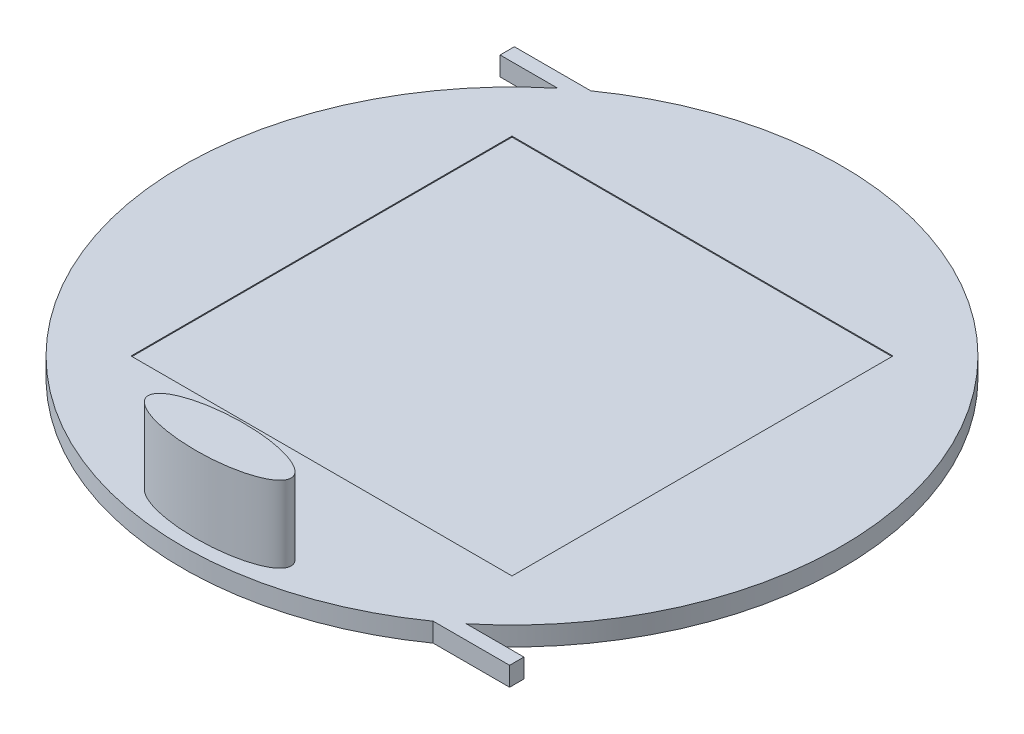
SolidWorks part; units mm, degrees
ref_plane "Front Plane" through (0, 0, 0) normal (0, 0, 1) x (1, 0, 0)
ref_plane "Top Plane" through (0, 0, 0) normal (0, 1, 0) x (1, 0, 0)
ref_plane "Right Plane" through (0, 0, 0) normal (1, 0, 0) x (0, 0, -1)
sketch "Sketch1" plane through (0, 0, 0) normal (0, 1, 0) x (1, 0, 0)
  line L0 (-2.5, -2) -> (2.5, -2) construction
  line L1 (2.5, -2) -> (0, 5) construction
  line L2 (0, 5) -> (-2.5, -2) construction
  line L3 (0, 0) -> (0, -2) construction
  line L4 (0, 5.7433) -> (-2.8548, -2.25)
  line L5 (-2.8548, -2.25) -> (2.8548, -2.25)
  line L6 (2.8548, -2.25) -> (0, 5.7433)
  line L7 (-32.9646, 10.5116) -> (-32.9646, -10.5116)
  line L8 (0, 27.5) -> (0, -27.5) construction
  line L9 (0, 27.5) -> (-28, 27.5)
  line L10 (0, -27.5) -> (28, -27.5)
  circle A0 centre (0, 0) radius 35 construction
  circle A1 centre (0, 0) radius 34.6
  dimension "D1" = 70
  dimension "D3" = 7
  dimension "D4" = 5
  dimension "D5" = 2
  dimension "D7" = 55
  dimension "D8" = 28
  dimension "D2" = 0.4
  dimension "D6" = 0.25
extrude "Boss-Extrude1" add sketch "Sketch1" along normal blind 2 contours L5 L6 L4 | A1 L6 L5 L4 | L7 A1 region at (0, 0, -0.4144) region at (-27.4961, 0, -19.3684) region at (-33.6201, 0, 0)
sketch "Sketch3" plane through (0, 2, 0) normal (0, 1, 0) x (1, 0, 0)
  line L0 (-7.5, -30.6947) -> (7.5, -30.6947) construction
  ellipse E0 centre (0, -30.6947) end of major axis (7.5, -30.6947) minor radius 2.5
  dimension "D1" = 5
  dimension "D2" = 15
extrude "Boss-Extrude2" add sketch "Sketch3" along normal blind 8
sketch "Sketch4" plane through (0, 2, 0) normal (0, 1, 0) x (1, 0, 0)
  line L1 (-20, 20) -> (20, 20)
  line L2 (-20, 20) -> (-20, -20)
  line L3 (-20, -20) -> (20, -20)
  line L4 (20, 20) -> (20, -20)
  line L5 (-20, 20) -> (20, -20) construction
  line L6 (-20, -20) -> (20, 20) construction
  point P0 (0, 0)
  dimension "D1" = 40
extrude "Cut-Extrude3" cut sketch "Sketch4" against normal blind 0.1
sketch "Sketch7" plane through (0, 0, 0) normal (0, 0, 1) x (1, 0, 0)
  line L0 (-34.6, 1) -> (-29.75, 0)
  line L1 (-34.6, 2) -> (-34.6, 0) construction
  line L2 (-34.6, 0) -> (34.6, 0) construction
  line L3 (-29.75, 0) -> (-34.6, 0)
  line L4 (-34.6, 0) -> (-34.6, 1)
extrude "Cut-Extrude4" cut sketch "Sketch7" against normal blind 21 and the other way blind 22 contours L3 L4 L0
extrude "Extrude-Thin1" add sketch "Sketch1<6>" along normal blind 2 thin contours L9 | L10 thin type mid plane wall 1.5
sketch "Sketch1<6>" plane through (0, 0, 0) normal (0, 1, 0) x (1, 0, 0) same geometry as "Sketch1"
